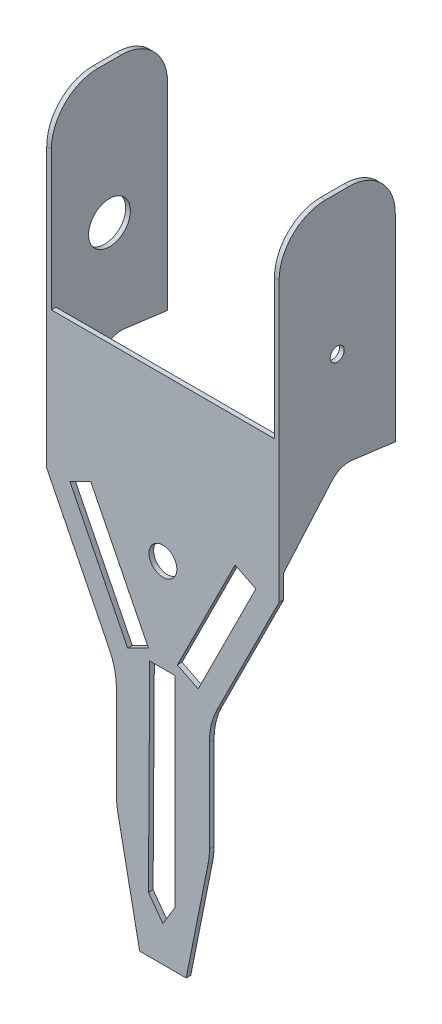
SolidWorks part; units mm, degrees
ref_plane "Alzado" through (0, 0, 0) normal (0, 0, 1) x (1, 0, 0)
ref_plane "Planta" through (0, 0, 0) normal (0, 1, 0) x (1, 0, 0)
ref_plane "Vista lateral" through (0, 0, 0) normal (1, 0, 0) x (0, 0, -1)
sketch "Croquis2" plane through (0, 0, 0) normal (0, 0, 1) x (1, 0, 0)
  line L1 (-32.8649, 52.5838) -> (17.1351, 52.5838)
  line L2 (-32.8649, 52.5838) -> (-32.8649, -97.4162)
  line L3 (-32.8649, -97.4162) -> (17.1351, -97.4162)
  line L4 (17.1351, 52.5838) -> (17.1351, -97.4162)
  dimension "D1" = 50
  dimension "D2" = 150
extrude "Saliente-Extruir1" add sketch "Croquis2" along normal blind 25
sketch "Croquis6" plane through (0, 0, 0) normal (0, 0, -1) x (-1, 0, 0)
  line L1 (-17.1351, 52.5838) -> (32.8649, 52.5838) construction
  line L2 (-16.1351, 52.5838) -> (-16.1351, 12.5838)
  line L4 (31.8649, 52.5838) -> (31.8649, 12.5838)
  line L5 (31.8649, 12.5838) -> (-16.1351, 12.5838)
  line L6 (-16.1351, 12.5838) -> (-16.1309, 12.4115)
  line L7 (-16.1351, 52.5838) -> (31.8649, 52.5838)
extrude "Cortar-Extruir1" cut sketch "Croquis6" against normal blind 25 contours L5 L4 L7 L2
shell "Vaciado2" thickness 1 removed face at (-7.8649, -97.4162, 12.5) removed face at (-7.8649, 12.5838, 12.5)
sketch "Croquis8" plane through (-32.8649, 0, 0) normal (-1, 0, 0) x (0, 0, 1)
  circle A0 centre (12.5, 22.5838) radius 4.5
  dimension "D1" = 9
extrude "Cortar-Extruir3" cut sketch "Croquis8" against normal blind 1
sketch "Croquis9" plane through (0, 0, 0) normal (0, 0, -1) x (-1, 0, 0)
  line L0 (-16.1351, 12.5838) -> (-16.1351, -97.4162)
  line L1 (32.8649, -97.4162) -> (-17.1351, -97.4162) construction
  line L2 (31.8649, 12.5838) -> (31.8649, -97.4162)
  line L3 (-16.1351, 12.5838) -> (31.8649, 12.5838)
  line L4 (-16.1351, -97.4162) -> (31.8649, -97.4162)
extrude "Cortar-Extruir4" cut sketch "Croquis9" against normal blind 10
sketch "Croquis10" plane through (-32.8649, 0, 0) normal (-1, 0, 0) x (0, 0, 1)
  line L0 (0, 0) -> (24, -12.4162)
  line L3 (24, -12.4162) -> (24, -97.4162)
  line L4 (25, -97.4162) -> (0, -97.4162) construction
  line L5 (24, -97.4162) -> (0, -97.4162)
  line L6 (0, -97.4162) -> (0, 0)
  dimension "D1" = 65
  dimension "D2" = 52.5838
extrude "Cortar-Extruir5" cut sketch "Croquis10" against normal blind 1
sketch "Croquis11" plane through (17.1351, 0, 0) normal (1, 0, 0) x (0, 0, -1)
  line L3 (-24, -12.4162) -> (-24, -97.4162)
  line L4 (-25, -97.4162) -> (0, -97.4162) construction
  line L5 (-24, -97.4162) -> (0, -97.4162)
  line L6 (0, -97.4162) -> (0, 0)
  line L7 (0, 0) -> (-24, -12.4162)
  circle A0 centre (-12.5, 22.5838) radius 1.5
  line M1 (0, -97.4162) -> (0, 52.5838)
  line M4 (-25, -97.4162) -> (0, -97.4162)
extrude "Cortar-Extruir6" cut sketch "Croquis11" against normal blind 1 contours L7 L3 M1 M4 region at (17.1351, -51.7417, 11.7277)
sketch "Croquis12" plane through (17.1351, 0, 0) normal (1, 0, 0) x (0, 0, -1)
  circle A0 centre (-12.5, 22.5838) radius 1.5
  dimension "D1" = 3
extrude "Cortar-Extruir7" cut sketch "Croquis12" against normal blind 1
sketch "Croquis13" plane through (0, 0, 25) normal (0, 0, 1) x (1, 0, 0)
  line L0 (-17.8649, -50.9572) -> (-17.8649, -70.9309)
  line L1 (-27.8649, -17.4162) -> (-23.3928, -15.1801)
  line L2 (-32.8649, -97.4162) -> (-12.8649, -97.4162)
  line L3 (-27.8649, -17.4162) -> (-15.4485, -42.249)
  line L4 (-32.8649, -17.4162) -> (-32.8649, -97.4162)
  line L5 (-32.8649, 52.5838) -> (-32.8649, -97.4162) construction
  line L6 (-32.8649, -17.4162) -> (-19.4485, -44.249)
  line L7 (-17.5736, -73.8726) -> (-12.8649, -97.4162)
  line L8 (-15.4485, -42.249) -> (-10.9764, -40.0129)
  line L9 (-2.8649, -97.4162) -> (1.8438, -73.8726)
  line L10 (2.1351, -70.9309) -> (2.1351, -50.9572)
  line L11 (3.7187, -44.249) -> (17.1351, -17.4162)
  line L12 (17.1351, -97.4162) -> (17.1351, 52.5838) construction
  line L13 (17.1351, -17.4162) -> (17.1351, -97.4162)
  line L14 (17.1351, -97.4162) -> (-2.8649, -97.4162)
  line L15 (-10.9764, -40.0129) -> (-23.3928, -15.1801)
  line L17 (12.1351, -17.4162) -> (-0.2813, -42.249)
  line L18 (-0.2813, -42.249) -> (-4.7534, -40.0129)
  line L19 (-4.7534, -40.0129) -> (7.663, -15.1801)
  line L20 (7.663, -15.1801) -> (12.1351, -17.4162)
  line L24 (-7.8649, -42.249) -> (-5.2855, -42.249)
  line L25 (-5.2855, -42.249) -> (-5.2855, -85.5126)
  line L26 (-5.2855, -85.5126) -> (-7.8649, -89.7959)
  line L27 (-7.8649, -89.7959) -> (-10.9764, -85.5126)
  line L28 (-10.9764, -85.5126) -> (-10.7092, -42.249)
  line L29 (-10.7092, -42.249) -> (-7.8649, -42.249)
  arc A0 (1.8438, -73.8726) -> (2.1351, -70.9309) centre (-12.8649, -70.9309) ccw
  arc A1 (2.1351, -50.9572) -> (3.7187, -44.249) centre (17.1351, -50.9572) cw
  arc A2 (-17.8649, -50.9572) -> (-19.4485, -44.249) centre (-32.8649, -50.9572) ccw
  arc A3 (-17.5736, -73.8726) -> (-17.8649, -70.9309) centre (-2.8649, -70.9309) cw
  circle A4 centre (-7.8649, -22.249) radius 3
  dimension "D1" = 80
  dimension "D2" = 15
extrude "Cortar-Extruir8" cut sketch "Croquis13" against normal blind 10
fillet "Redondeo1" radius 10 4 edges at (16.6351, 52.5838, 0) (16.6351, 52.5838, 25) (-32.3649, 52.5838, 0) (-32.3649, 52.5838, 25)
sketch "Croquis14" plane through (-32.8649, 0, 0) normal (-1, 0, 0) x (0, 0, 1)
  line L0 (0, 0) -> (9.2359, 1.2007)
  line L1 (13.6591, -0.4831) -> (24, -12.4162)
  line L2 (24, -12.4162) -> (0, 0)
  arc A0 (9.2359, 1.2007) -> (13.6591, -0.4831) centre (9.8805, -3.7575) cw
  dimension "D1" = 5
extrude "Cortar-Extruir9" cut sketch "Croquis14" against normal blind 50
